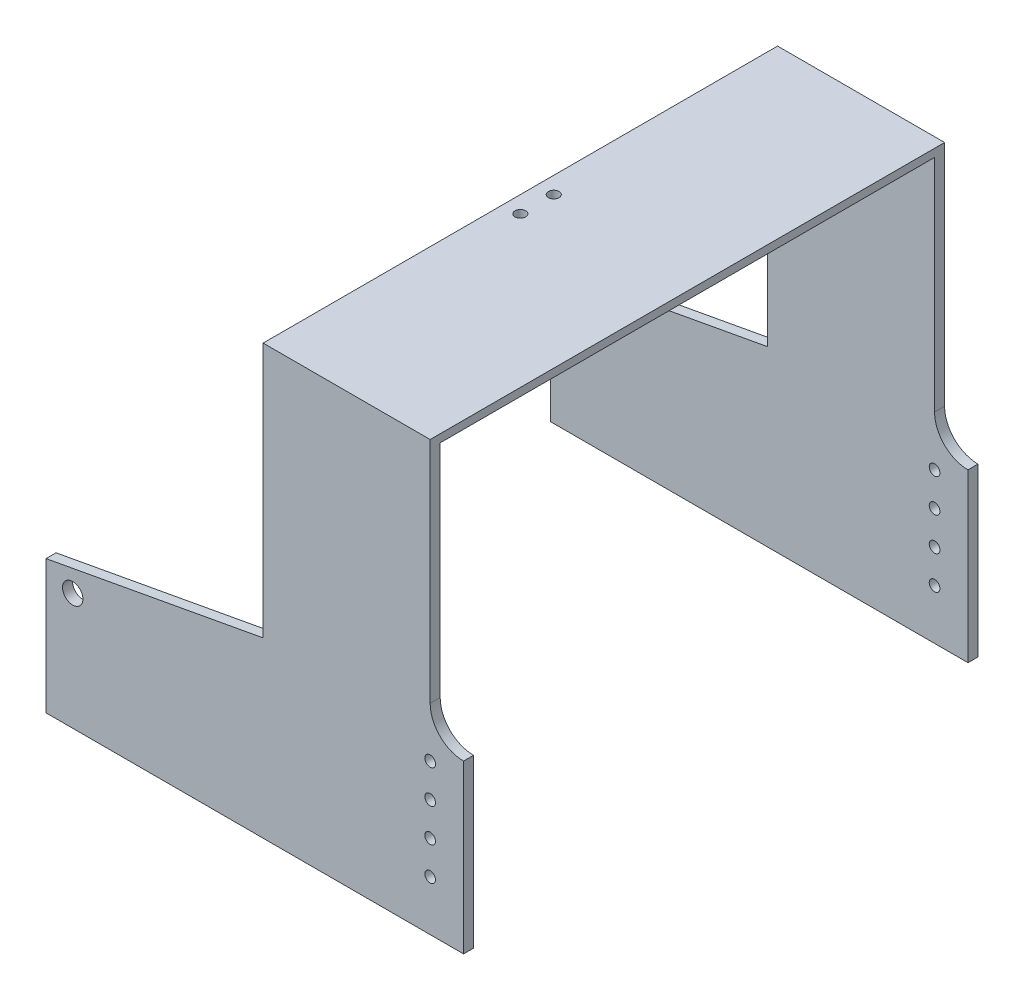
SolidWorks part; units mm, degrees
ref_plane "前视基准面" through (0, 0, 0) normal (0, 0, 1) x (1, 0, 0)
ref_plane "上视基准面" through (0, 0, 0) normal (0, 1, 0) x (1, 0, 0)
ref_plane "右视基准面" through (0, 0, 0) normal (1, 0, 0) x (0, 0, -1)
other "Configuration Table"
sketch "草图1" plane through (0, 0, 0) normal (0, 0, 1) x (1, 0, 0)
  line L0 (3.2926, 24.5764) -> (3.2926, -25.4236)
  line L1 (3.2926, -25.4236) -> (-121.7074, -25.4236)
  line L2 (-121.7074, -25.4236) -> (-121.7074, 14.5764)
  line L3 (-121.7074, 14.5764) -> (-56.7074, 26.5151)
  line L4 (-6.7074, 24.5764) -> (3.2926, 24.5764)
  line L5 (-6.7074, 24.5764) -> (-6.7074, -25.4236) construction
  line L6 (-56.7074, 26.5151) -> (-56.7074, 102.946)
  line L7 (-56.7074, 102.946) -> (-6.7074, 102.946)
  line L8 (-6.7074, 102.946) -> (-6.7074, 24.5764)
  circle A0 centre (-6.7074, -10.4236) radius 1.6
  circle A1 centre (-6.7074, -0.4236) radius 1.6
  circle A2 centre (-6.7074, 9.5764) radius 1.6
  circle A3 centre (-6.7074, 19.5764) radius 1.6
  dimension "D3" = 3.2
  dimension "D7" = 10
  dimension "D1" = 40
  dimension "D2" = 50
  dimension "D4" = 15
  dimension "D5" = 10
  dimension "D6" = 125
  dimension "D8" = 10
  dimension "D9" = 50
  dimension "D10" = 10
extrude "凸台-拉伸1" add sketch "草图1" along normal blind 154
sketch "草图5" plane through (0, 0, 154) normal (0, 0, 1) x (1, 0, 0)
  line L1 (-121.7074, -25.4236) -> (-113.7074, -25.4236) construction
  line L2 (-121.7074, -25.4236) -> (-121.7074, 9.5764) construction
  line L3 (-121.7074, 9.5764) -> (-113.7074, 9.5764) construction
  line L4 (-113.7074, -25.4236) -> (-113.7074, 9.5764) construction
  circle A0 centre (-113.7074, 9.5764) radius 3.05
  dimension "D1" = 6.1
  dimension "D2" = 8
  dimension "D3" = 35
extrude "切除-拉伸3" cut sketch "草图5" against normal through all
sketch "草图6" plane through (0, -25.4236, 0) normal (0, -1, 0) x (1, 0, 0)
  line L0 (-121.7074, 154) -> (-121.7074, 0) construction
  line L1 (-121.7074, 151) -> (3.2926, 151)
  line L2 (-121.7074, 151) -> (-121.7074, 3)
  line L3 (-121.7074, 3) -> (3.2926, 3)
  line L4 (3.2926, 151) -> (3.2926, 3)
  line L5 (3.2926, 154) -> (3.2926, 0) construction
  line L6 (-121.7074, 0) -> (3.2926, 0) construction
  line L7 (-121.7074, 154) -> (3.2926, 154) construction
  dimension "D1" = 3
  dimension "D2" = 3
extrude "切除-拉伸5" cut sketch "草图6" against normal blind 126
sketch "草图7" plane through (0, 102.946, 0) normal (0, 1, 0) x (1, 0, 0)
  line L0 (-56.7074, -154) -> (-56.7074, 0) construction
  line L1 (-56.7074, -82) -> (-51.7074, -82) construction
  line L2 (-56.7074, -82) -> (-56.7074, -72) construction
  line L3 (-56.7074, -72) -> (-51.7074, -72) construction
  line L4 (-51.7074, -82) -> (-51.7074, -72) construction
  circle A0 centre (-51.7074, -82) radius 1.6
  circle A1 centre (-51.7074, -72) radius 1.6
  point P6 (-56.7074, -77)
  point P7 (-56.7074, -77)
  dimension "D3" = 3.2
  dimension "D1" = 10
  dimension "D2" = 5
extrude "切除-拉伸6" cut sketch "草图7" against normal blind 119 contours A1 | A0 | L2 L1 L4 L3 region at (-51.7074, 102.946, 82) region at (-51.7074, 102.946, 72)
fillet "圆角1" radius 10 2 edges at (-6.7074, 24.5764, 1.5) (-6.7074, 24.5764, 152.5)
